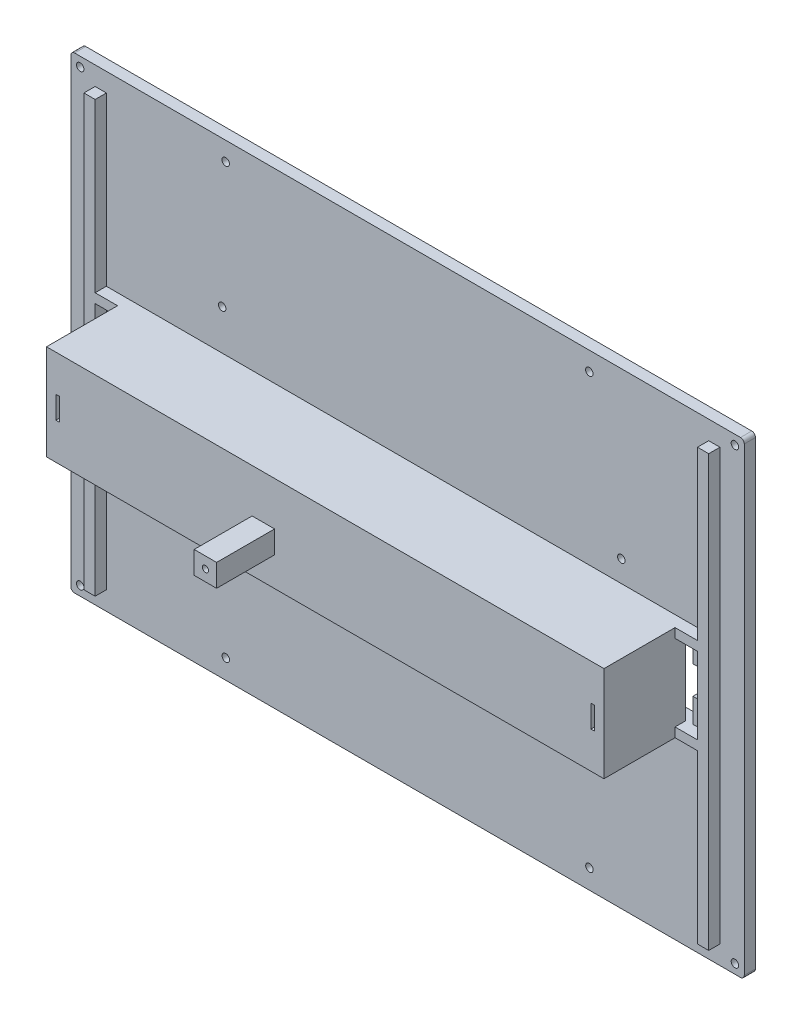
SolidWorks part; units mm, degrees
ref_plane "前视基准面" through (0, 0, 0) normal (0, 0, 1) x (1, 0, 0)
ref_plane "上视基准面" through (0, 0, 0) normal (0, 1, 0) x (1, 0, 0)
ref_plane "右视基准面" through (0, 0, 0) normal (1, 0, 0) x (0, 0, -1)
sketch "草图1" plane through (0, 0, 0) normal (0, 0, 1) x (1, 0, 0)
  line L1 (-90, 62.5) -> (90, 62.5)
  line L2 (-90, 62.5) -> (-90, -62.5)
  line L3 (-90, -62.5) -> (90, -62.5)
  line L4 (90, 62.5) -> (90, -62.5)
  line L5 (-90, 62.5) -> (90, -62.5) construction
  line L6 (-90, -62.5) -> (90, 62.5) construction
  point P0 (0, 0)
  dimension "D1" = 125
  dimension "D2" = 180
extrude "凸台-拉伸1" add sketch "草图1" along normal blind 3
sketch "草图7" plane through (0, 0, 0) normal (0, 0, -1) x (-1, 0, 0)
  line L1 (-72, 10.25) -> (72, 10.25)
  line L2 (-72, 10.25) -> (-72, -10.25)
  line L3 (-72, -10.25) -> (72, -10.25)
  line L4 (72, 10.25) -> (72, -10.25)
  line L5 (0, 0) -> (72.729, 0) construction
  line L8 (0, 0) -> (0, -50.9103) construction
  dimension "D1" = 20.5
  dimension "D2" = 144
extrude "电池位切除-拉伸3" cut sketch "草图7" against normal up to next
sketch "草图8" plane through (0, 0, 3) normal (0, 0, 1) x (1, 0, 0)
  line L12 (72, 10.25) -> (72, -10.25) construction
  line L13 (-74.5, 12.75) -> (74.5, 12.75)
  line L14 (-74.5, 12.75) -> (-74.5, -12.75)
  line L15 (-74.5, -12.75) -> (74.5, -12.75)
  line L16 (74.5, 12.75) -> (74.5, -12.75)
  line L17 (-72, -10.25) -> (-72, 10.25) construction
  line L18 (-72, 10.25) -> (72, 10.25) construction
  line L19 (72, -10.25) -> (-72, -10.25) construction
  line L20 (-72, 10.25) -> (72, 10.25)
  line L21 (72, -10.25) -> (-72, -10.25)
  line L22 (72, 10.25) -> (72, -10.25)
  line L23 (-72, -10.25) -> (-72, 10.25) construction
  line L24 (-72, -10.25) -> (-72, 10.25)
  dimension "D1" = 2.5
  dimension "D2" = 2.5
  dimension "D3" = 2.5
  dimension "D4" = 2.5
extrude "凸台-拉伸2" add sketch "草图8" along normal blind 22
sketch "草图9" plane through (0, 0, 25) normal (0, 0, 1) x (1, 0, 0)
  line L0 (74.5, 12.75) -> (-74.5, 12.75) construction
  line L5 (74.5, 12.75) -> (-74.5, 12.75)
  line L6 (-74.5, -12.75) -> (74.5, -12.75) construction
  line L7 (-74.5, -12.75) -> (74.5, -12.75)
  line L8 (74.5, -12.75) -> (74.5, 12.75) construction
  line L9 (74.5, -12.75) -> (74.5, 12.75)
  line L10 (-74.5, 12.75) -> (-74.5, -12.75) construction
  line L11 (-74.5, 12.75) -> (-74.5, -12.75)
extrude "凸台-拉伸3" add sketch "草图9" against normal blind 2.5
sketch "草图4" plane through (0, 0, 0) normal (0, 0, -1) x (-1, 0, 0)
  line L0 (72, -10.25) -> (72, 10.25) construction
  line L5 (72, 0) -> (84.6307, 0) construction
  line L10 (83.2374, -53.4277) -> (79.3374, -53.4277) construction
  line L11 (83.2374, -49.6277) -> (83.2374, -53.4277) construction
  line L12 (79.3374, -49.6277) -> (83.2374, -49.6277) construction
  line L29 (72, -4) -> (74.5, -4)
  line L30 (74.5, -4) -> (74.5, 4)
  line L31 (74.5, 4) -> (72, 4)
  line L32 (72, 4) -> (72, -4)
  dimension "D1" = 8
  dimension "D2" = 2.5
extrude "切除-拉伸2" cut sketch "草图4" against normal blind 2 from offset 1.5 offset against normal yes
sketch "草图10" plane through (0, 0, 25) normal (0, 0, 1) x (1, 0, 0)
  line L0 (-16.5366, -1.9347) -> (8.5541, -1.9347) construction
  line L2 (-19.5366, 1.0653) -> (-19.5366, -4.9347)
  line L4 (-13.5366, 1.0653) -> (-13.5366, -4.9347)
  line L5 (-16.5366, -1.9347) -> (-16.5366, 4.0653) construction
  line L6 (0, 0) -> (60.8594, 0) construction
  line L7 (0, 0) -> (0, 60.5) construction
  line L8 (75, 60.5) -> (-75, 60.5) construction
  line L9 (-19.5366, 1.0653) -> (-13.5366, 1.0653)
  line L10 (-19.5366, -4.9347) -> (-13.5366, -4.9347)
  circle A0 centre (-16.5366, -1.9347) radius 0.825
  dimension "D2" = 1.65
  dimension "D1" = 6
extrude "凸台-拉伸4" add sketch "草图10" along normal up to surface (15.5 mm away)
sketch "草图11" plane through (0, 0, 0) normal (0, 0, -1) x (-1, 0, 0)
  circle A0 centre (-48.6147, -57.3) radius 1 construction
  circle A1 centre (-49.55, -23.3) radius 1 construction
  circle A2 centre (57.15, -18.3) radius 1 construction
  circle A3 centre (48.5747, -57.3) radius 1 construction
  circle A4 centre (87.5, 60) radius 1
  circle A5 centre (48.6147, 57.5) radius 1 construction
  circle A6 centre (-57.15, 18.5) radius 1 construction
  circle A7 centre (-48.5747, 57.5) radius 1 construction
  circle A8 centre (-48.6147, -57.3) radius 1
  circle A9 centre (-49.55, -23.3) radius 1
  circle A10 centre (57.15, -18.3) radius 1
  circle A11 centre (48.5747, -57.3) radius 1
  circle A13 centre (48.6147, 57.5) radius 1
  circle A14 centre (-57.15, 18.5) radius 1
  circle A15 centre (-48.5747, 57.5) radius 1
  circle A16 centre (49.55, 23.5) radius 1 construction
  circle A17 centre (49.55, 23.5) radius 1
  circle A18 centre (87.5, -60) radius 1
  circle A19 centre (-87.5, -60) radius 1
  circle A20 centre (-87.5, 60) radius 1
  dimension "D1" = 2
  dimension "D2" = 2
  dimension "D3" = 2
  dimension "D4" = 2
extrude "固定螺丝切除-拉伸3" cut sketch "草图11" against normal up to next
sketch "草图12" plane through (0, 0, 0) normal (0, 0, -1) x (-1, 0, 0)
  circle A0 centre (-48.5747, 57.5) radius 2
  circle A1 centre (-57.15, 18.5) radius 2
  circle A2 centre (-49.55, -23.3) radius 2
  circle A3 centre (-48.6147, -57.3) radius 2
  circle A4 centre (48.5747, -57.3) radius 2
  circle A5 centre (57.15, -18.3) radius 2
  circle A7 centre (-87.5, 60) radius 2
  circle A8 centre (48.6147, 57.5) radius 2
  circle A9 centre (49.55, 23.5) radius 2
  circle A10 centre (-87.5, -60) radius 2
  circle A11 centre (87.5, -60) radius 2
  circle A12 centre (87.5, 60) radius 2
  dimension "D1" = 4
  dimension "D2" = 4
  dimension "D3" = 4
  dimension "D4" = 4
  dimension "D5" = 4
extrude "固定螺丝凹陷切除-拉伸4" cut sketch "草图12" against normal blind 1.2
fillet "圆角1" radius 1 4 edges at (90, -62.5, 1.5) (-90, -62.5, 1.5) (-90, 62.5, 1.5) (90, 62.5, 1.5)
sketch "草图13" plane through (0, 0, 25) normal (0, 0, 1) x (1, 0, 0)
  line L0 (72, 10.25) -> (72, -10.25) construction
  line L1 (72, 3) -> (71, 3)
  line L2 (72, 3) -> (72, -3)
  line L3 (72, -3) -> (71, -3)
  line L4 (71, 3) -> (71, -3)
  line L5 (-72, -10.25) -> (-72, 10.25) construction
  line L6 (-71, 3) -> (-72, 3)
  line L7 (-71, 3) -> (-71, -3)
  line L8 (-71, -3) -> (-72, -3)
  line L9 (-72, 3) -> (-72, -3)
  line L10 (72, 0) -> (59.7453, 0) construction
  dimension "D1" = 1
  dimension "D2" = 6
  dimension "D3" = 1
  dimension "D4" = 6
extrude "切除-拉伸3" cut sketch "草图13" against normal up to next
sketch "草图14" plane through (0, 0, 22.5) normal (0, 0, -1) x (-1, 0, 0)
  line L0 (72, 10.25) -> (-72, 10.25) construction
  line L1 (-71, 10.25) -> (-69, 10.25)
  line L2 (-71, 10.25) -> (-71, 5.25)
  line L3 (-71, 5.25) -> (-69, 5.25)
  line L4 (-69, 10.25) -> (-69, 5.25)
  line L5 (-72, 0) -> (-60.8543, 0) construction
  line L6 (-72, 10.25) -> (-72, -10.25) construction
  line L7 (72, 0) -> (63.4917, 0) construction
  line L8 (69, 10.25) -> (71, 10.25)
  line L9 (69, 10.25) -> (69, 5.75)
  line L10 (69, 5.75) -> (71, 5.75)
  line L11 (71, 10.25) -> (71, 5.75)
  line L12 (72, -10.25) -> (72, 10.25) construction
  line L13 (71, -10.25) -> (71, -5.75)
  line L14 (69, -5.75) -> (71, -5.75)
  line L15 (69, -10.25) -> (69, -5.75)
  line L16 (69, -10.25) -> (71, -10.25)
  line L17 (-69, -10.25) -> (-69, -5.25)
  line L18 (-71, -5.25) -> (-69, -5.25)
  line L19 (-71, -10.25) -> (-71, -5.25)
  line L20 (-71, -10.25) -> (-69, -10.25)
  dimension "D1" = 1
  dimension "D2" = 2
  dimension "D3" = 4.5
  dimension "D4" = 1
  dimension "D5" = 2
  dimension "D6" = 5
extrude "凸台-拉伸5" add sketch "草图14" along normal blind 16
sketch "草图15" plane through (0, 0, 0) normal (0, 0, -1) x (-1, 0, 0)
  line L7 (-72, -10.25) -> (72, -10.25) construction
  line L8 (-76.3, 10.25) -> (-72, 10.25)
  line L9 (-76.3, 10.25) -> (-76.3, 3.75)
  line L10 (-76.3, -10.25) -> (-72, -10.25)
  line L11 (-72, 10.25) -> (-72, -10.25)
  line L12 (-76.3, 3.75) -> (-79.3365, 3.75)
  line L14 (-76.3, -3.75) -> (-79.3365, -3.75)
  line L15 (-79.3365, 3.75) -> (-79.3365, -3.75)
  line L16 (72, 10.25) -> (-72, 10.25) construction
  line L17 (-76.3, -3.75) -> (-76.3, -10.25)
  line L18 (-76.1, -10.05) -> (-76.1, 10.05) construction
  line L19 (-79.2365, 3.5) -> (-79.2365, -3.5) construction
  dimension "D1" = 6.5
  dimension "D2" = 6.5
  dimension "D3" = 0.2
  dimension "D4" = 0.1
extrude "切除-拉伸6" cut sketch "草图15" against normal blind 3.2
sketch "草图17" plane through (0, 0, 0) normal (0, 0, -1) x (-1, 0, 0)
  line L0 (-76.3, 3.75) -> (-79.3365, 3.75) construction
  line L1 (-81.8365, 3.75) -> (-79.3365, 3.75)
  line L2 (-81.8365, 3.75) -> (-81.8365, -3.75)
  line L3 (-81.8365, -3.75) -> (-79.3365, -3.75)
  line L4 (-79.3365, 3.75) -> (-79.3365, -3.75)
  dimension "D1" = 2.5
extrude "切除-拉伸7" cut sketch "草图17" against normal blind 1.5
fillet "圆角2" radius 0.25 26 edges at (-71, 10.25, 14.5) (-69, 10.25, 14.5) (-69, -10.25, 14.5) (-71, -10.25, 14.5) (71, -10.25, 14.5) (69, -10.25, 14.5) (69, 10.25, 14.5) (71, 10.25, 14.5) (-70, 10.25, 6.5) (-71, 8, 6.5) (-70, 5.75, 6.5) (-69, 8, 6.5) (-69, -8, 6.5) (-70, -5.75, 6.5) (-71, -8, 6.5) (-70, -10.25, 6.5) (71, -7.75, 6.5) (70, -5.25, 6.5) (69, -7.75, 6.5) (70, -10.25, 6.5) (70, 10.25, 6.5) (69, 7.75, 6.5) (70, 5.25, 6.5) (71, 7.75, 6.5) (79.3365, 0, 3) (81.8365, 0, 0)
sketch "草图18" plane through (0, 0, 3) normal (0, 0, 1) x (1, 0, 0)
  line L0 (0, 0) -> (0, 49.5083) construction
  line L1 (-83.5, 57.5) -> (-80.5, 57.5)
  line L2 (-83.5, 57.5) -> (-83.5, -57.5)
  line L3 (-83.5, -57.5) -> (-80.5, -57.5)
  line L4 (-80.5, 57.5) -> (-80.5, 12.75)
  line L5 (89, 62.5) -> (-89, 62.5) construction
  line L6 (-89, -62.5) -> (89, -62.5) construction
  line L7 (-74.5, 12.75) -> (-74.5, -12.75) construction
  line L12 (-80.5, 10.25) -> (-80.5, -10.25)
  line L13 (-74.5, 12.75) -> (-80.5, 12.75)
  line L14 (-74.5, 12.75) -> (-74.5, 10.25)
  line L15 (-74.5, 10.25) -> (-80.5, 10.25)
  line L17 (-74.5, -12.75) -> (-80.5, -12.75)
  line L18 (-74.5, -12.75) -> (-74.5, -10.25)
  line L19 (-74.5, -10.25) -> (-80.5, -10.25)
  line L21 (-80.5, -12.75) -> (-80.5, -57.5)
  line L22 (80.5, -12.75) -> (80.5, -57.5)
  line L23 (74.5, -10.25) -> (80.5, -10.25)
  line L24 (74.5, -12.75) -> (74.5, -10.25)
  line L25 (74.5, -12.75) -> (80.5, -12.75)
  line L26 (74.5, 10.25) -> (80.5, 10.25)
  line L27 (74.5, 12.75) -> (74.5, 10.25)
  line L28 (74.5, 12.75) -> (80.5, 12.75)
  line L29 (80.5, 10.25) -> (80.5, -10.25)
  line L30 (80.5, 57.5) -> (80.5, 12.75)
  line L31 (83.5, -57.5) -> (80.5, -57.5)
  line L32 (83.5, 57.5) -> (83.5, -57.5)
  line L33 (83.5, 57.5) -> (80.5, 57.5)
  dimension "D1" = 5
  dimension "D2" = 5
  dimension "D3" = 3
  dimension "D4" = 6
  dimension "D5" = 2.5
extrude "凸台-拉伸6" add sketch "草图18" along normal blind 3
